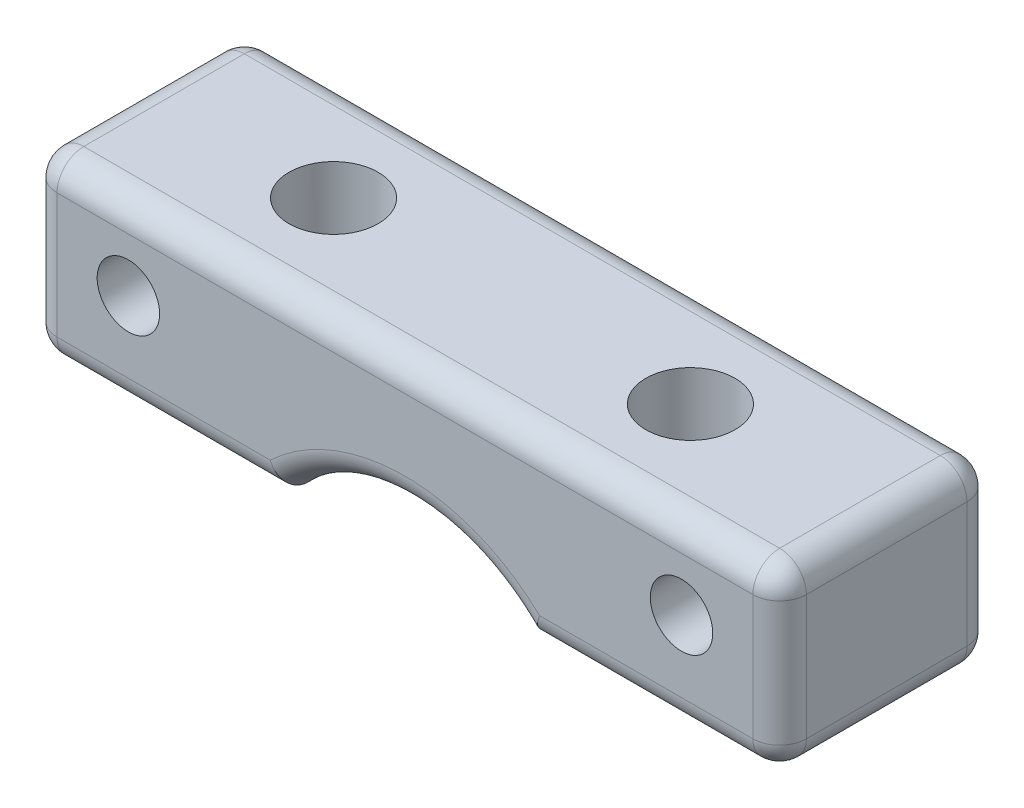
SolidWorks part; units mm, degrees
material "1060 Alloy"
ref_plane "Front Plane" through (0, 0, 0) normal (0, 0, 1) x (1, 0, 0)
ref_plane "Top Plane" through (0, 0, 0) normal (0, 1, 0) x (1, 0, 0)
ref_plane "Right Plane" through (0, 0, 0) normal (1, 0, 0) x (0, 0, -1)
sketch "Sketch1" plane through (0, 0, 0) normal (0, 1, 0) x (1, 0, 0)
  line L0 (0, -55) -> (0, 55) construction
  line L1 (21, 6) -> (-21, 6)
  line L2 (21, 6) -> (21, -6)
  line L3 (21, -6) -> (-21, -6)
  line L4 (-21, 6) -> (-21, -6)
  line L5 (21, 6) -> (-21, -6) construction
  line L6 (21, -6) -> (-21, 6) construction
  circle A0 centre (-10, 0) radius 2.5
  circle A1 centre (10, 0) radius 2.5
  point P0 (0, 0)
  dimension "D3" = 5
  dimension "D4" = 6
  dimension "D5" = 11
  dimension "D1" = 42
  dimension "D2" = 12
extrude "main boss" add sketch "Sketch1" along normal blind 10
sketch "Sketch2" plane through (0, 0, 6) normal (0, 0, 1) x (1, 0, 0)
  line L0 (-21, 10) -> (21, 10) construction
  line L1 (-21, 10) -> (-21, 0) construction
  line L3 (21, 10) -> (21, 0) construction
  line L4 (0, -5.5) -> (0, 5.5) construction
  circle A0 centre (-15.5, 5.5) radius 1.75
  circle A1 centre (15.5, 5.5) radius 1.75
  circle A2 centre (0, -6.5) radius 9.5
  dimension "D1" = 3.5
  dimension "D2" = 4.5
  dimension "D3" = 19
  dimension "D5" = 5.5
  dimension "D6" = 21
  dimension "D4" = 16.5
extrude "side holes" cut sketch "Sketch2" against normal through all
fillet "Fillet2" radius 1.5 16 edges at (-21, 5, -6) (-21, 10, 0) (-21, 5, 6) (-21, 0, 0) (21, 5, 6) (21, 10, 0) (21, 5, -6) (21, 0, 0) (13.9641, 0, 6) (0, 3, 6) (-13.9641, 0, 6) (13.9641, 0, -6) (-13.9641, 0, -6) (0, 3, -6) (0, 10, -6) (0, 10, 6)
chamfer "Chamfer2" distance 3 angle 45 2 edges at (-10, 0, 2.5) (10, 0, -2.5)
